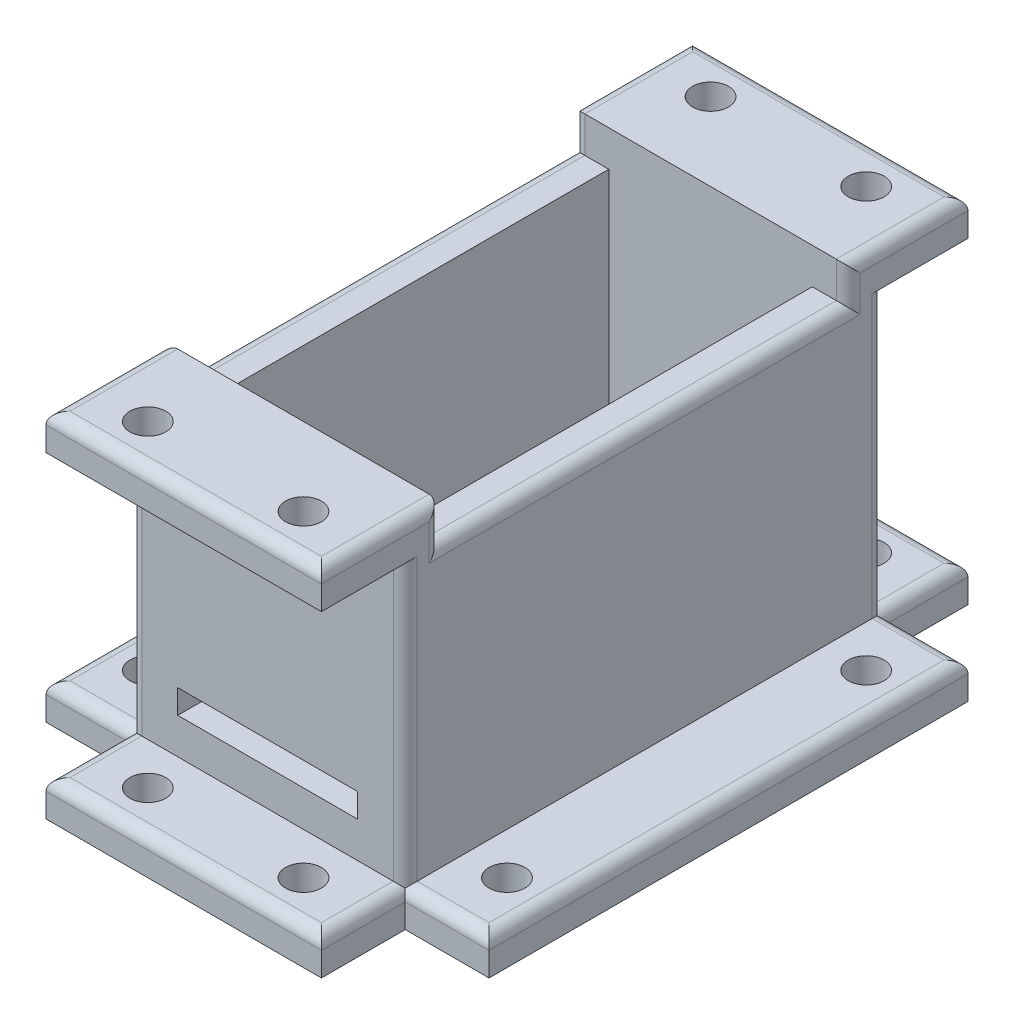
SolidWorks part; units mm, degrees
ref_plane "Alzado" through (0, 0, 0) normal (0, 0, 1) x (1, 0, 0)
ref_plane "Planta" through (0, 0, 0) normal (0, 1, 0) x (1, 0, 0)
ref_plane "Vista lateral" through (0, 0, 0) normal (1, 0, 0) x (0, 0, -1)
sketch "Croquis2" plane through (0, 0, 0) normal (0, 1, 0) x (1, 0, 0)
  line L1 (0, 0) -> (-23, 0)
  line L2 (0, 0) -> (0, 40)
  line L3 (0, 40) -> (-23, 40)
  line L4 (-23, 0) -> (-23, 40)
  dimension "D1" = 40
  dimension "D2" = 23
extrude "Saliente-Extruir1" add sketch "Croquis2" along normal blind 23.5
sketch "Croquis3" plane through (0, 23.5, 0) normal (0, 1, 0) x (1, 0, 0)
  line L0 (0, 40) -> (-23, 40) construction
  line L1 (-20, 37) -> (-3, 37)
  line L2 (-20, 37) -> (-20, 3)
  line L3 (-20, 3) -> (-3, 3)
  line L4 (-3, 37) -> (-3, 3)
  line L5 (-23, 40) -> (-23, 0) construction
  line L6 (-23, 0) -> (0, 0) construction
  line L7 (0, 0) -> (0, 40) construction
  dimension "D1" = 3
  dimension "D2" = 3
  dimension "D3" = 3
  dimension "D4" = 3
extrude "Cortar-Extruir1" cut sketch "Croquis3" against normal blind 13.5
sketch "Croquis4" plane through (0, 0, 0) normal (0, -1, 0) x (1, 0, 0)
  line L1 (0, -40) -> (-23, -40) construction
  line L2 (-17, -40) -> (-30, -40)
  line L3 (-17, -40) -> (-17, 0)
  line L4 (-17, 0) -> (-30, 0)
  line L5 (-30, -40) -> (-30, 0)
  line L6 (-23, -40) -> (-23, 0) construction
  line L7 (-23, -40) -> (-23, 0) construction
  line L8 (-23, -6) -> (0, -6)
  line L9 (-23, -6) -> (-23, 7)
  line L10 (-23, 7) -> (0, 7)
  line L11 (0, -6) -> (0, 7)
  line L12 (-23, 0) -> (0, 0) construction
  line L13 (0, 0) -> (0, -40) construction
  line L14 (-6, -40) -> (7, -40)
  line L15 (-6, -40) -> (-6, 0)
  line L16 (-6, 0) -> (7, 0)
  line L17 (7, -40) -> (7, 0)
  line L19 (-23, -34) -> (0, -34)
  line L20 (-23, -34) -> (-23, -47)
  line L21 (-23, -47) -> (0, -47)
  line L22 (0, -34) -> (0, -47)
  point P7 (-23, -20)
  line M13 (0, -40) -> (0, 0)
  line M14 (0, 0) -> (-23, 0)
  line M15 (-23, 0) -> (-23, -40)
  line M16 (-23, -40) -> (0, -40)
  dimension "D1" = 7
  dimension "D2" = 7
  dimension "D3" = 7
  dimension "D4" = 7
  dimension "D5" = 13
  dimension "D6" = 23
  dimension "D7" = 40
  dimension "D8" = 40
  dimension "D9" = 23
  dimension "D10" = 13
  dimension "D11" = 13
  dimension "D12" = 13
extrude "Saliente-Extruir6" add sketch "Croquis4" along normal blind 3 contours L19 L3 L8 M15 | L8 L3 M15 M14 | L5 L2 L4 M15 | L11 L10 L9 M14 | L19 L3 M15 M16 | L19 L3 L15 M16 | L19 L15 M16 M13 | L15 L19 L8 M13 | L15 L8 M13 M14 | L8 L15 L3 M14 | L14 L17 L16 M13 | L22 L21 L20 L19 region at (-20, 0, -37) region at (-11.5, 0, -37) region at (-26.5, 0, -20) region at (-20, 0, -20) region at (-3, 0, -37) region at (-20, 0, -3) region at (-11.5, 0, -3) region at (-3, 0, -20) region at (3.5, 0, -20) region at (-11.5, 0, 3.5) region at (-3, 0, -3)
sketch "Croquis6" plane through (0, 0, 0) normal (0, 1, 0) x (1, 0, 0)
  line L0 (-30, 40) -> (-30, 0) construction
  line L1 (-30, 40) -> (-23, 40) construction
  line L2 (-23, 0) -> (-30, 0) construction
  line L3 (-23, 40) -> (-23, 47) construction
  line L4 (0, 40) -> (0, 47) construction
  line L5 (-23, 47) -> (0, 47) construction
  line L6 (-30, 20) -> (15.9373, 20) construction
  line L7 (-11.5, 47) -> (-11.5, -15.5258) construction
  circle A0 centre (-26.5, 5) radius 1.5
  circle A1 centre (-26.5, 35) radius 1.5
  circle A2 centre (-18, 43.5) radius 1.5
  circle A3 centre (-5, 43.5) radius 1.5
  circle A4 centre (3.5, 5) radius 1.5
  circle A5 centre (3.5, 35) radius 1.5
  circle A6 centre (-5, -3.5) radius 1.5
  circle A7 centre (-18, -3.5) radius 1.5
  dimension "D1" = 3
  dimension "D2" = 3
  dimension "D3" = 3.5
  dimension "D5" = 5
  dimension "D6" = 3.5
  dimension "D7" = 3
  dimension "D8" = 3
  dimension "D9" = 5
  dimension "D10" = 5
  dimension "D11" = 3.5
  dimension "D12" = 3.5
  dimension "D4" = 5
extrude "Cortar-Extruir2" cut sketch "Croquis6" against normal through all
sketch "Croquis7" plane through (0, 23.5, 0) normal (0, 1, 0) x (1, 0, 0)
  line L1 (-23, 40) -> (-23, 0) construction
  line L2 (-23, 37) -> (0, 37)
  line L3 (-23, 37) -> (-23, 47)
  line L4 (-23, 47) -> (0, 47)
  line L5 (0, 37) -> (0, 47)
  line L6 (-3, 37) -> (-20, 37) construction
  line L10 (-20, 3) -> (-3, 3) construction
  line L13 (-23, 3) -> (0, 3)
  line L14 (-23, 3) -> (-23, -7)
  line L15 (-23, -7) -> (0, -7)
  line L16 (0, 3) -> (0, -7)
  circle A0 centre (-18, -3.5) radius 1.5
  circle A1 centre (-5, -3.5) radius 1.5
  circle A2 centre (-18, 43.5) radius 1.5
  circle A3 centre (-5, 43.5) radius 1.5
  dimension "D5" = 3
  dimension "D6" = 3
  dimension "D7" = 3
  dimension "D4" = 3
  dimension "D1" = 23
  dimension "D2" = 10
  dimension "D3" = 10
extrude "Saliente-Extruir7" add sketch "Croquis7" along normal blind 3
fillet "Redondeo1" radius 1 4 edges at (0, 11.75, 0) (-23, 11.75, 0)
fillet "Redondeo2" radius 1 12 edges at (-23, 0, 3.5) (-11.5, 0, 7) (0, 0, 3.5) (3.5, 0, 0) (3.5, 0, -40) (7, 0, -20) (-11.5, 0, -47) (-23, 0, -43.5) (0, 0, -43.5) (-26.5, 0, -40) (-30, 0, -20) (-26.5, 0, 0)
fillet "Redondeo3" radius 1 12 edges at (0, 25, -3) (-23, 25, -3) (0, 26.5, 2) (-23, 26.5, 2) (-11.5, 26.5, 7) (0, 26.5, -42) (-11.5, 26.5, -47) (-23, 26.5, -42)
sketch "Croquis8" plane through (0, -3, 0) normal (0, -1, 0) x (-1, 0, 0)
  line L1 (20, 3) -> (3, 3)
  line L2 (20, 3) -> (20, 37)
  line L3 (20, 37) -> (3, 37)
  line L4 (3, 3) -> (3, 37)
extrude "Cortar-Extruir3" cut sketch "Croquis8" against normal through all
sketch "Croquis9" plane through (0, 0, -40) normal (0, 0, -1) x (-1, 0, 0)
  line L0 (1, 23.5) -> (1, 0) construction
  line L1 (4, 5) -> (19, 5)
  line L2 (4, 5) -> (4, 3)
  line L3 (4, 3) -> (19, 3)
  line L4 (19, 5) -> (19, 3)
  line L5 (22, 0) -> (22, 23.5) construction
  line L6 (1, 0) -> (22, 0) construction
  dimension "D1" = 3
  dimension "D2" = 3
  dimension "D3" = 2
  dimension "D4" = 3
extrude "Cortar-Extruir4" cut sketch "Croquis9" against normal through all
